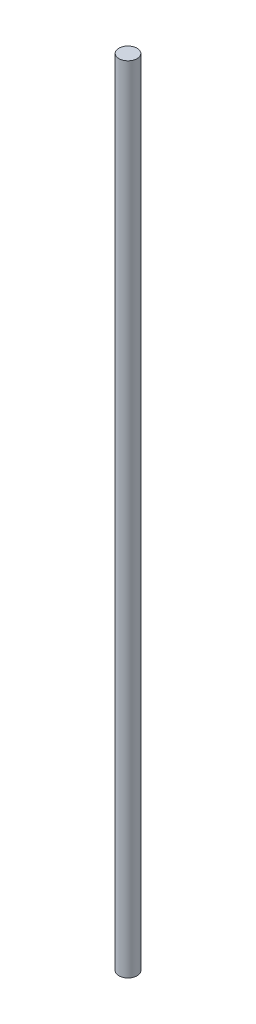
SolidWorks part; units mm, degrees
material "AISI 1020"
ref_plane "Front Plane" through (0, 0, 0) normal (0, 0, 1) x (1, 0, 0)
ref_plane "Top Plane" through (0, 0, 0) normal (0, 1, 0) x (1, 0, 0)
ref_plane "Right Plane" through (0, 0, 0) normal (1, 0, 0) x (0, 0, -1)
sketch "Sketch1" plane through (0, 0, 0) normal (0, 1, 0) x (1, 0, 0)
  circle A0 centre (0, 0) radius 4
  dimension "D1" = 8
extrude "Boss-Extrude1" add sketch "Sketch1" along normal blind 175 and the other way blind 175
cosmetic thread "Cosmetic Thread1"
